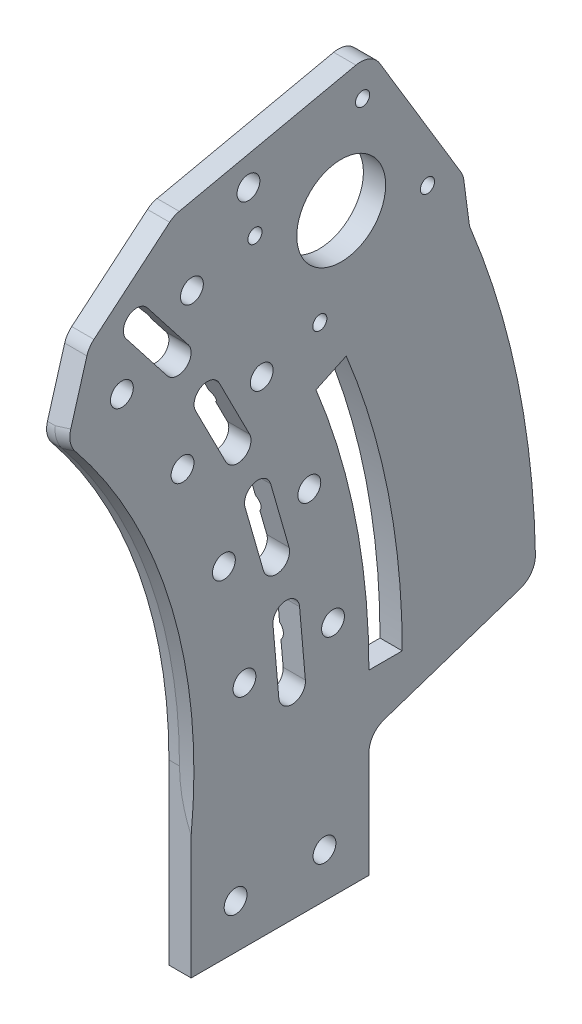
SolidWorks part; units mm, degrees
other "Markup1"
sketch "Sketch5" plane through (7.4724, -50.8, -116.7452) normal (0.7166, -0.0822, 0.6926) x (0.6913, -0.0479, -0.721)
other "Markup2"
sketch "Sketch6" plane through (7.4724, -50.8, -116.7452) normal (0.7166, -0.0822, 0.6926) x (0.6913, -0.0479, -0.721)
material "6061-T6 (SS)"
ref_plane "Front Plane" through (0, 0, 0) normal (0, 0, 1) x (1, 0, 0)
ref_plane "Top Plane" through (0, 0, 0) normal (0, 1, 0) x (1, 0, 0)
ref_plane "Right Plane" through (0, 0, 0) normal (1, 0, 0) x (0, 0, -1)
sketch "Sketch1" plane through (0, 0, 0) normal (1, 0, 0) x (0, 0, -1)
  line L0 (0, 0) -> (152.4, 0) construction
  line L1 (0, 0) -> (116.7452, 97.9608) construction
  line L2 (152.4, 0) -> (152.4, -50.8)
  line L3 (152.4, -50.8) -> (203.2, -50.8)
  line L4 (203.2, -50.8) -> (203.2, 0) construction
  line L5 (116.7452, 97.9608) -> (148.2956, 124.4347) construction
  line L6 (152.4, 0) -> (203.2, 0) construction
  line L7 (116.7452, 97.9608) -> (148.2956, 124.4347) construction
  line L8 (0, 0) -> (177.1234, 15.4963) construction
  line L9 (0, 0) -> (0, 168.3639) construction
  line L10 (177.1234, 15.4963) -> (183.4493, 16.0497) construction
  line L11 (0, 0) -> (175.0988, 30.8746) construction
  line L12 (0, 0) -> (171.7416, 46.018) construction
  line L13 (0, 0) -> (167.0773, 60.8112) construction
  line L14 (0, 0) -> (161.1415, 75.1415) construction
  line L15 (0, 0) -> (153.9793, 88.9) construction
  line L16 (0, 0) -> (145.6452, 101.9819) construction
  line L17 (0, 0) -> (175.0988, 30.8746) construction
  line L18 (0, 0) -> (171.7416, 46.018) construction
  line L19 (183.4493, 16.0497) -> (196.1009, 17.1566) construction
  line L20 (181.3523, 31.9773) -> (193.8594, 34.1826) construction
  line L21 (177.8752, 47.6615) -> (190.1425, 50.9485) construction
  line L22 (173.0444, 62.983) -> (184.9785, 67.3267) construction
  line L23 (166.8966, 77.8252) -> (178.4067, 83.1924) construction
  line L24 (159.4786, 92.075) -> (170.4771, 98.425) construction
  line L25 (150.8468, 105.6241) -> (161.2501, 112.9085) construction
  line L26 (0, 0) -> (183.4493, 16.0497) construction
  line L27 (0, 0) -> (181.3523, 31.9773) construction
  line L28 (152.4, -50.8) -> (152.4, -38.1) construction
  line L29 (152.4, -38.1) -> (203.2, -38.1) construction
  line L30 (0, 0) -> (42824.6192, 25807.9831) construction
  line L31 (195.2803, 117.6844) -> (182.1698, 139.4393) construction
  line L32 (195.2803, 117.6844) -> (208.3907, 95.9295) construction
  line L33 (217.0352, 130.7949) -> (203.9247, 152.5498)
  line L34 (217.0352, 130.7949) -> (230.1456, 109.04)
  line L36 (177.6941, 146.8661) -> (203.9247, 152.5498)
  line L37 (196.7125, 80.97) -> (212.8664, 88.5027) construction
  line L38 (188.0704, 76.9401) -> (212.8664, 88.5027) construction
  line L39 (212.8664, 88.5027) -> (230.1456, 109.04) construction
  line L40 (196.7125, 80.97) -> (188.0704, 76.9401)
  line L41 (203.2, 0) -> (212.725, 0)
  line L42 (203.2, -15.875) -> (250.825, 0)
  line L43 (230.1456, 109.04) -> (231.9445, 95.472)
  line L44 (203.2, -50.8) -> (203.2, -15.875)
  line L45 (195.2803, 117.6844) -> (190.7375, 99.3622) construction
  line L47 (0, 0) -> (136.2027, 114.2876) construction
  line L48 (116.7452, 97.9608) -> (123.1425, 119.9075)
  line L49 (123.1425, 119.9075) -> (147.4644, 140.316)
  line L50 (147.4644, 140.316) -> (177.6941, 146.8661)
  line L51 (189.1677, 93.0309) -> (195.2803, 117.6844) construction
  line L52 (195.2803, 117.6844) -> (201.3928, 142.3379) construction
  arc A0 (152.4, 0) -> (116.7452, 97.9608) centre (0, 0) ccw
  arc A1 (203.2, 0) -> (188.0704, 76.9401) centre (0, 0) ccw
  circle A2 centre (177.1234, 15.4963) radius 6.35 construction
  arc A4 (183.4493, 16.0497) -> (141.0671, 118.3693) centre (0, 0) ccw construction
  arc A5 (189.7751, 16.6032) -> (145.9315, 122.451) centre (0, 0) ccw construction
  circle A7 centre (196.1009, 17.1566) radius 6.35 construction
  circle A9 centre (175.0988, 30.8746) radius 6.35 construction
  circle A11 centre (171.7416, 46.018) radius 6.35 construction
  circle A13 centre (167.0773, 60.8112) radius 6.35 construction
  circle A15 centre (161.1415, 75.1415) radius 6.35 construction
  circle A17 centre (153.9793, 88.9) radius 6.35 construction
  circle A19 centre (145.6452, 101.9819) radius 6.35 construction
  circle A21 centre (193.8594, 34.1826) radius 6.35 construction
  circle A23 centre (190.1425, 50.9485) radius 6.35 construction
  circle A25 centre (184.9785, 67.3267) radius 6.35 construction
  circle A27 centre (178.4067, 83.1924) radius 6.35 construction
  circle A29 centre (170.4771, 98.425) radius 6.35 construction
  circle A31 centre (161.2501, 112.9085) radius 6.35 construction
  circle A32 centre (165.1, -38.1) radius 3.2639
  circle A33 centre (190.5, -38.1) radius 3.2639
  circle A34 centre (195.2803, 117.6844) radius 12.7
  circle A36 centre (208.3907, 95.9295) radius 2.0193 construction
  arc A37 (196.7125, 80.97) -> (212.725, 0) centre (0, 0) cw
  arc A38 (231.9445, 95.472) -> (250.825, 0) centre (0, 0) cw
  circle A41 centre (170.6267, 123.797) radius 2.0193
  circle A42 centre (201.3928, 142.3379) radius 2.0193
  circle A45 centre (195.2803, 117.6844) radius 12.7
  circle A46 centre (219.9338, 111.5719) radius 2.0193
  circle A47 centre (195.2803, 117.6844) radius 12.7
  circle A48 centre (189.1677, 93.0309) radius 2.0193
  circle A49 centre (195.2803, 117.6844) radius 12.7
  point P11 (151.8201, 13.2825)
  point P24 (150.0847, 26.464)
  point P82 (217.0352, 130.7949)
  point P124 (195.2803, 117.6844)
  dimension "D5" = 12.7
  dimension "D7" = 22.86
  dimension "D12" = 12.7
  dimension "D24" = 6.5278
  dimension "D25" = 6.5278
  dimension "D28" = 25.4
  dimension "D30" = 25.4
  dimension "D32" = 4.0386
  dimension "D35" = 9.525
  dimension "D43" = 4.0386
  dimension "D1" = 152.4
  dimension "D2" = 40
  dimension "D3" = 50.8
  dimension "D4" = 50.8
  dimension "D6" = 5
  dimension "D8" = 25.4
  dimension "D10" = 90
  dimension "D13" = 25.4
  dimension "D14" = 5
  dimension "D16" = 5
  dimension "D17" = 6.35
  dimension "D20" = 5
  dimension "D21" = 12.7
  dimension "D22" = 12.7
  dimension "D23" = 12.7
  dimension "D26" = 8.925
  dimension "D27" = 228
  dimension "D29" = 25.4
  dimension "D31" = 25.4
  dimension "D33" = 25.4
  dimension "D34" = 25.4
  dimension "D37" = 15.875
  dimension "D38" = 45
  dimension "D41" = 12.7
  dimension "D42" = 31.75
  dimension "D9" = 6.35
  dimension "D36" = 38.1
  dimension "D15" = 6
  dimension "D19" = 7
  dimension "D45" = 4
extrude "Boss-Extrude1" add sketch "Sketch1" along normal blind 6.35 contours A38 L43 L34 L33 L36 L50 L49 L48 A0 L2 L3 L44 L42 A48 A46 A42 A41 A34 A33 A32 region at (0, 54.4796, -185.6582)
sketch "Sketch2" plane through (0, 0, 0) normal (0, 1, 0) x (1, 0, 0)
  line L0 (0, 0) -> (31.75, 0) construction
  line L1 (31.75, 0) -> (31.75, 38.1) construction
  line L2 (31.75, 38.1) -> (-86.106, 38.1)
  line L3 (-86.106, 38.1) -> (149.606, 38.1)
  arc A0 (149.606, 38.1) -> (-86.106, 38.1) centre (31.75, 38.1) ccw
  dimension "D3" = 235.712
  dimension "D1" = 31.75
  dimension "D2" = 38.1
revolve "Cut-Revolve1" cut sketch "Sketch2" angle 360 about L0 region at (31.75, 0, -88.1196)
fillet "Fillet1" radius 6.35 9 edges at (3.175, -15.875, -203.2) (3.175, 0, -250.825) (3.175, 95.472, -231.9445) (3.175, 109.04, -230.1456) (3.175, 152.5498, -203.9247) (3.175, 140.316, -147.4644) (3.175, 119.9075, -123.1425) (1.5088, 97.9608, -116.7452)
sketch "Sketch7" plane through (0, 0, 0) normal (0, 0, 1) x (1, 0, 0)
  line L0 (0, 0) -> (50000, 0) construction
sketch "Sketch8" plane through (0, 0, 0) normal (-1, 0, 0) x (0, 0, 1)
  line L0 (0, 0) -> (-192.938, 16.8799) construction
  line L1 (0, 0) -> (-81.6847, 0) construction
  line L2 (0, 0) -> (-186.1724, 53.3841) construction
  line L3 (0, 0) -> (-172.5657, 87.9266) construction
  line L4 (0, 0) -> (-152.618, 119.2382) construction
  line L5 (-175.7872, 24.9408) -> (-177.4475, 5.9633)
  line L6 (-167.7986, 58.0243) -> (-173.0495, 39.7123)
  line L7 (0, 0) -> (-167.6347, 14.6661) construction
  line L8 (0, 0) -> (-161.7563, 46.3829) construction
  line L9 (-177.4475, 5.9633) -> (-175.7872, 24.9408) construction
  line L10 (-175.7872, 24.9408) -> (-183.3782, 25.6049) construction
  line L11 (-183.3782, 25.6049) -> (-185.0385, 6.6274)
  line L12 (-185.0385, 6.6274) -> (-177.4475, 5.9633) construction
  line L13 (-180.3743, 41.8126) -> (-173.0495, 39.7123) construction
  line L15 (-167.7986, 58.0243) -> (-175.1234, 60.1247) construction
  line L16 (-175.1234, 60.1247) -> (-180.3743, 41.8126)
  line L17 (-169.0821, 75.4615) -> (-162.2926, 72.002) construction
  line L19 (-153.6441, 88.9757) -> (-160.4335, 92.4351) construction
  line L20 (-160.4335, 92.4351) -> (-169.0821, 75.4615)
  line L21 (-151.5768, 106.3374) -> (-145.5722, 101.6461) construction
  line L23 (-133.8438, 116.6577) -> (-139.8485, 121.349) construction
  line L24 (-139.8485, 121.349) -> (-151.5768, 106.3374)
  line L25 (-173.0495, 39.7123) -> (-167.7986, 58.0243) [skipped]
  line L27 (-162.2926, 72.002) -> (-153.6441, 88.9757) [skipped]
  line L28 (-153.6441, 88.9757) -> (-162.2926, 72.002)
  line L30 (-145.5722, 101.6461) -> (-133.8438, 116.6577) [skipped]
  line L34 (-145.5722, 101.6461) -> (-133.8438, 116.6577)
  circle A0 centre (-192.938, 16.8799) radius 3.2639
  arc A1 (-183.3782, 25.6049) -> (-175.7872, 24.9408) centre (-179.5827, 25.2728) cw
  circle A2 centre (-167.6347, 14.6661) radius 3.2639
  circle A3 centre (-186.1724, 53.3841) radius 3.2639
  circle A4 centre (-161.7563, 46.3829) radius 3.2639
  circle A5 centre (-172.5657, 87.9266) radius 3.2639
  circle A6 centre (-149.9341, 76.3953) radius 3.2639
  circle A7 centre (-152.618, 119.2382) radius 3.2639
  circle A8 centre (-132.6025, 103.6004) radius 3.2639
  arc A13 (-185.0385, 6.6274) -> (-177.4475, 5.9633) centre (-181.243, 6.2953) ccw
  arc A14 (-180.3743, 41.8126) -> (-173.0495, 39.7123) centre (-176.7119, 40.7625) ccw
  arc A15 (-175.1234, 60.1247) -> (-167.7986, 58.0243) centre (-171.461, 59.0745) cw
  arc A16 (-169.0821, 75.4615) -> (-162.2926, 72.002) centre (-165.6873, 73.7318) ccw
  arc A17 (-160.4335, 92.4351) -> (-153.6441, 88.9757) centre (-157.0388, 90.7054) cw
  arc A18 (-139.8485, 121.349) -> (-133.8438, 116.6577) centre (-136.8461, 119.0033) cw
  arc A19 (-151.5768, 106.3374) -> (-145.5722, 101.6461) centre (-148.5745, 103.9917) ccw
  dimension "D3" = 6.5278
  dimension "D4" = 6.5278
  dimension "D1" = 193.675
  dimension "D2" = 5
  dimension "D5" = 25.4
  dimension "D7" = 11
  dimension "D8" = 19.05
  dimension "D9" = 7.62
  dimension "D10" = 9.525
  dimension "D11" = 9.017
  dimension "D6" = 4
extrude "Cut-Extrude1" cut sketch "Sketch8" against normal through all
sketch "Sketch9" plane through (0, 16.1161, -184.2084) normal (0, -0.0872, 0.9962) x (1, 0, 0)
  line L0 (0, 0) -> (-2.3812, 0) construction
  line L1 (0, 9.525) -> (0, -9.525) construction
  circle A0 centre (-2.3812, 0) radius 3.2639
  dimension "D1" = 6.5278
  dimension "D2" = 2.3812
extrude "Cut-Extrude2" cut sketch "Sketch9" against normal blind 3.175 and the other way blind 10.033
pattern_circular "CirPattern1" count 4 every 11 about axis through (0, 0, 0) along (1, 0, 0) of "Cut-Extrude2"
sketch "Sketch10" plane through (0, 0, 0) normal (-1, 0, 0) x (0, 0, 1)
  line L0 (0, 0) -> (-168.7728, 136.6695) construction
  line L1 (0, 0) -> (-65.3997, 0) construction
  circle A0 centre (-168.7728, 136.6695) radius 3.2639
  dimension "D1" = 6.5278
  dimension "D2" = 217.17
  dimension "D3" = 39
extrude "Cut-Extrude3" cut sketch "Sketch10" against normal through all
